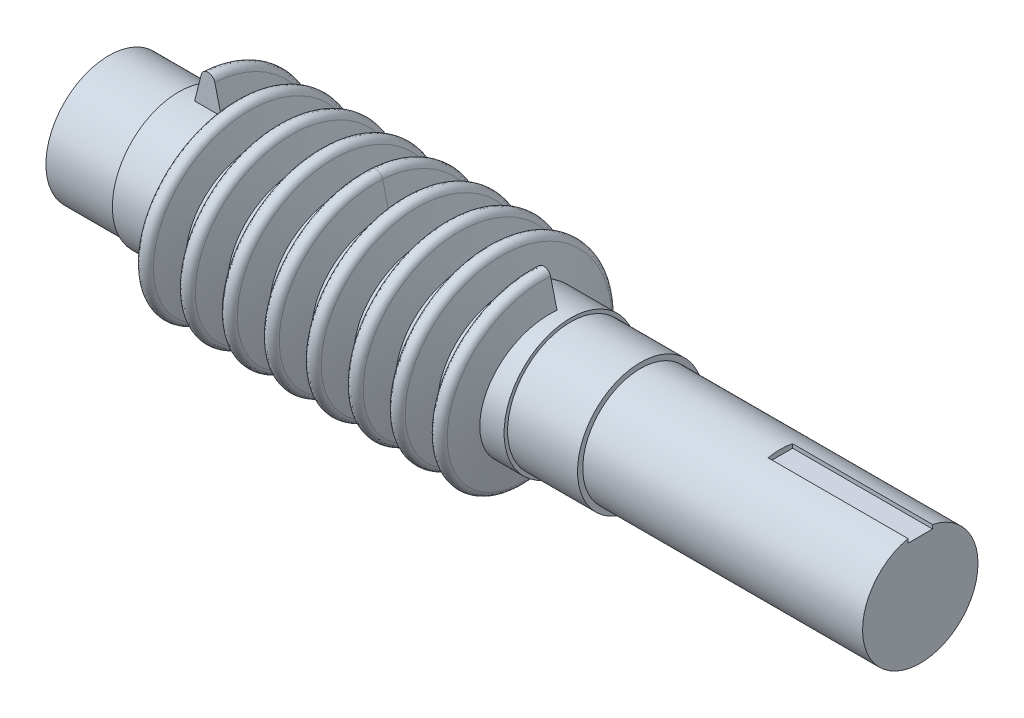
SolidWorks part; units mm, degrees
ref_plane "Front Plane" through (0, 0, 0) normal (0, 0, 1) x (1, 0, 0)
ref_plane "Top Plane" through (0, 0, 0) normal (0, 1, 0) x (1, 0, 0)
ref_plane "Right Plane" through (0, 0, 0) normal (1, 0, 0) x (0, 0, -1)
sketch "Sketch1" plane through (0, 0, 0) normal (0, 0, 1) x (1, 0, 0)
  line L0 (78, -11.75) -> (-38, -11.75)
  line L1 (-38, -11.75) -> (-38, -2.75)
  line L2 (-38, -2.75) -> (-28, -2.75)
  line L3 (-28, -2.75) -> (-28, -2.25)
  line L4 (-28, -2.25) -> (28, -2.25)
  line L5 (28, -2.25) -> (28, -2.75)
  line L6 (28, -2.75) -> (38, -2.75)
  line L7 (38, -2.75) -> (38, -3.5)
  line L8 (38, -3.5) -> (78, -3.5)
  line L9 (78, -3.5) -> (78, -11.75)
  dimension "D1" = 9.5
  dimension "D2" = 9
  dimension "D3" = 116
  dimension "D4" = 10
  dimension "D5" = 8.25
  dimension "D6" = 10
  dimension "D7" = 9
  dimension "D8" = 38
  dimension "D9" = 11.75
revolve "Revolve1" add sketch "Sketch1" angle 360 about L0
sketch "Sketch2" plane through (0, 0, 0) normal (1, 0, 0) x (0, 0, -1)
  circle A0 centre (0, -11.75) radius 9.5 construction
  circle A1 centre (0, -11.75) radius 9.5
curve "Helix/Spiral1" pitch 6 height 24 radius 9.5 left hand yes centre (0, -11.75, 0) axis (1, 0, 0) start towards (0, 1, 0)
sketch "Sketch3" plane through (0, 0, 0) normal (0, 0, 1) x (1, 0, 0)
  line L0 (0.1723, 1.25) -> (0.1723, -3.6321) construction
  line L2 (28, -2.25) -> (-28, -2.25) construction
  line L3 (1.1428, 1.4911) -> (2.0723, -2.25)
  line L4 (2.0723, -2.25) -> (2.0723, -2.6908)
  line L5 (-1.7277, -2.25) -> (-1.7277, -2.6908)
  line L6 (-0.7982, 1.4911) -> (-1.7277, -2.25)
  line L7 (-1.7277, -2.6908) -> (2.0723, -2.6908)
  arc A0 (1.1428, 1.4911) -> (-0.7982, 1.4911) centre (0.1723, 1.25) ccw
  dimension "D2" = 2
  dimension "D1" = 3.5
  dimension "D3" = 3.8
sweep "Sweep1" add profiles "Sketch3" path "Helix/Spiral1"
sketch "Sketch5" plane through (0, 0, 0) normal (1, 0, 0) x (0, 0, -1)
  circle A0 centre (0, -11.75) radius 8.25 construction
  circle A1 centre (0, -11.75) radius 8.25
curve "Helix/Spiral2" pitch 6 height 24 radius 8.25 left hand yes centre (0, -11.75, 0) axis (-1, 0, 0) start towards (0, 1, 0)
sketch "Sketch6" plane through (0, 0, 0) normal (0, 0, 1) x (1, 0, 0)
sweep "Sweep2" add profiles "Sketch3<2>" path "Helix/Spiral2"
sketch "Sketch3<2>" plane through (0, 0, 0) normal (0, 0, 1) x (1, 0, 0) same geometry as "Sketch3"
ref_plane "Plane1" through (78, 0, 0) normal (1, 0, 0) x (0, 0, -1)
sketch "Sketch8" plane through (78, 0, 0) normal (1, 0, 0) x (0, 0, -1)
  line L0 (0, -20) -> (0, -3.5) construction
  line L1 (0, -3.5) -> (0, -11.75) construction
  line L2 (0, -11.75) -> (2.6895, -11.75) construction
  line L4 (-1.75, -2.75) -> (1.75, -2.75)
  line L5 (-1.75, -2.75) -> (-1.75, -4.25)
  line L6 (-1.75, -4.25) -> (1.75, -4.25)
  line L7 (1.75, -2.75) -> (1.75, -4.25)
  line L8 (-1.75, -2.75) -> (1.75, -4.25) construction
  line L9 (-1.75, -4.25) -> (1.75, -2.75) construction
  circle A0 centre (0, -11.75) radius 8.25 construction
  dimension "D1" = 3.5
  dimension "D2" = 1.5
extrude "Cut-Extrude1" cut sketch "Sketch8" against normal blind 20
